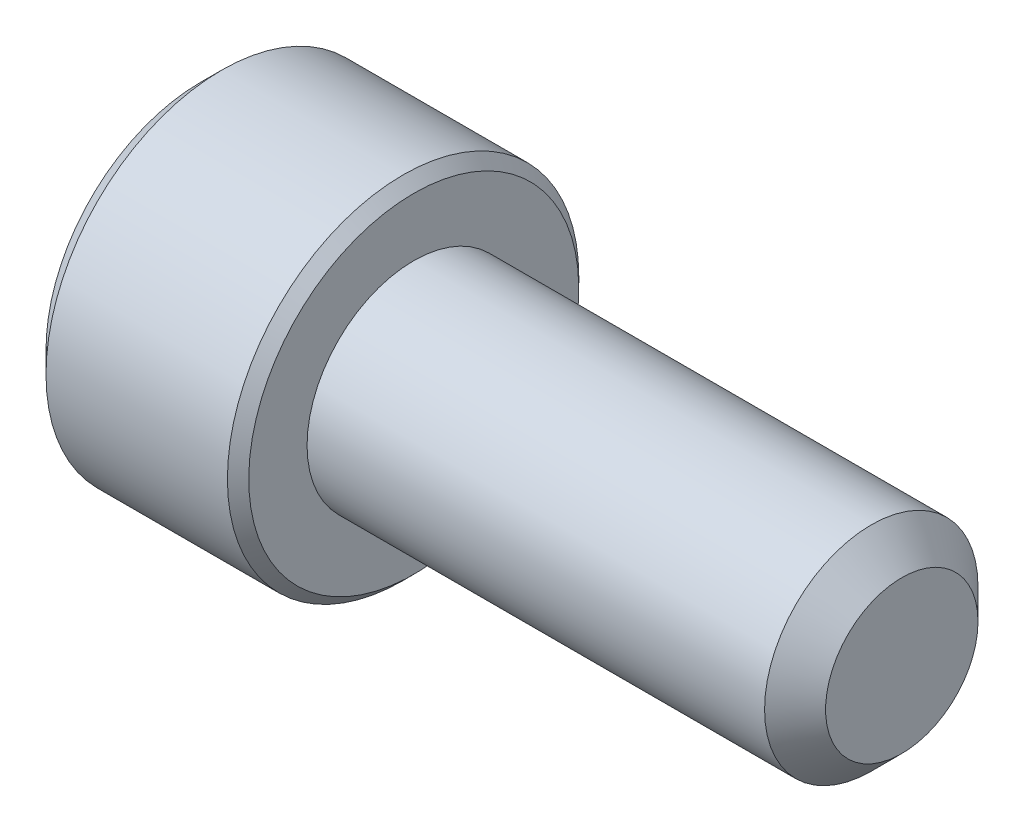
SolidWorks part; units mm, degrees
material "Alloy Steel"
ref_plane "Front Plane" through (0, 0, 0) normal (0, 0, 1) x (1, 0, 0)
ref_plane "Top Plane" through (0, 0, 0) normal (0, 1, 0) x (1, 0, 0)
ref_plane "Right Plane" through (0, 0, 0) normal (1, 0, 0) x (0, 0, -1)
sketch "Sketch1" plane through (0, 0, 0) normal (0, 0, 1) x (1, 0, 0)
  line L0 (4.7625, 0) -> (-4.7625, 0) construction
  line L1 (4.7625, 2.0828) -> (4.7625, -2.0828) construction
  line L2 (-4.7625, 3.2207) -> (-4.7625, -3.2207) construction
  line L3 (-4.9708, 3.429) -> (-8.5115, 3.429) construction
  line L4 (-8.5115, 3.429) -> (-8.9281, 3.0124) construction
  line L5 (-8.9281, 3.0124) -> (-8.9281, -3.0124) construction
  line L6 (-8.9281, -3.0124) -> (-8.5115, -3.429) construction
  line L7 (-8.5115, -3.429) -> (-4.9708, -3.429) construction
  line L8 (-4.9708, 3.429) -> (-4.7625, 3.2207) construction
  line L9 (-4.7625, -3.2207) -> (-4.9708, -3.429) construction
  point P5 (-4.7625, 3.429)
  point P6 (-4.7625, -3.429)
  point P7 (-6.2492, 0)
  point P12 (1.5875, -2.0828)
  dimension "D1" = 45
  dimension "D2" = 3.175
  dimension "D3" = 0.2083
ref_plane "Plane1" through (4.7625, 0, 0) normal (1, 0, 0) x (0, 0, -1)
ref_plane "Plane2" through (-8.9281, 0, 0) normal (1, 0, 0) x (0, 0, -1)
sketch "Sketch2" plane through (4.7625, 0, 0) normal (1, 0, 0) x (0, 0, -1)
  circle A0 centre (0, 0) radius 2.0828
extrude "Boss-Extrude1" add sketch "Sketch2" against normal up to vertex (9.525 mm away) up to point (-4.7625, 0, 0)
sketch "Sketch3" plane through (4.7625, 0, 0) normal (1, 0, 0) x (0, 0, -1)
  circle A0 centre (0, 0) radius 2.0828 construction
  circle A1 centre (0, 0) radius 2.0828
curve "Helix/Spiral1" pitch 0.7937 height 10.3187 turns 13 parameters "Pitch"=0.7937
chamfer "Chamfer1" distance 0.5953 angle 45 1 edges at (4.7625, 0, -2.0828)
sketch "Sketch5" plane through (0, 0, 0) normal (0, 0, 1) x (1, 0, 0)
  line L0 (4.4152, 2.0828) -> (5.1098, 2.0828)
  line L1 (5.1098, 2.0828) -> (4.8121, 1.5672)
  line L2 (4.8121, 1.5672) -> (4.7129, 1.5672)
  line L3 (4.7129, 1.5672) -> (4.4152, 2.0828)
  line L4 (4.7625, 1.5672) -> (4.7625, 2.0828) construction
  line L5 (4.5641, 1.825) -> (4.9609, 1.825) construction
  dimension "D1" = 60
  dimension "D2" = 0.3969
  dimension "D3" = 0.0992
sweep "Cut-Sweep1" [suppressed] cut profiles "Sketch5" path "Helix/Spiral1"
sketch "Sketch4" plane through (-8.9281, 0, 0) normal (1, 0, 0) x (0, 0, -1)
  line L0 (-3.429, 0.7937) -> (3.429, 0.7937) construction
  line L1 (0, 2.0622) -> (-1.7859, 1.0311)
  line L2 (-1.7859, 1.0311) -> (-1.7859, -1.0311)
  line L3 (-1.7859, -1.0311) -> (0, -2.0622)
  line L4 (0, -2.0622) -> (1.7859, -1.0311)
  line L5 (1.7859, -1.0311) -> (1.7859, 1.0311)
  line L6 (1.7859, 1.0311) -> (0, 2.0622)
  line L7 (0, 0) -> (0, 0.7937) construction
  circle A0 centre (0, 0) radius 1.7859 construction
  dimension "D1" = 6.858
  dimension "D2" = 0.7937
sketch "Sketch6" plane through (0, 0, 0) normal (0, 0, 1) x (1, 0, 0)
  line L0 (-8.5115, 3.429) -> (-8.9281, 3.0124) construction
  line L2 (-4.7625, 3.2207) -> (-4.7625, -3.2207) construction
  line L3 (-8.9281, 3.0124) -> (-8.9281, -3.0124) construction
  line L4 (-8.5115, 3.429) -> (-8.9281, 3.0124)
  line L5 (-4.9708, 3.429) -> (-8.5115, 3.429) construction
  line L6 (-4.7625, 3.2207) -> (-4.7625, 0)
  line L7 (-8.9281, 3.0124) -> (-8.9281, 0)
  line L8 (-4.7625, 0) -> (-8.9281, 0) construction
  line L9 (-4.7625, 0) -> (-8.9281, 0)
  line L10 (-4.9708, 3.429) -> (-4.7625, 3.2207) construction
  line L11 (-4.9708, 3.429) -> (-8.5115, 3.429)
  line L12 (-4.9708, 3.429) -> (-4.7625, 3.2207)
revolve "Revolve1" add sketch "Sketch6" angle 360 about L8
extrude "Cut-Extrude1" cut sketch "Sketch4" along normal up to vertex (2.6789 mm away) up to point (-6.2492, 0, 0)
sketch "Sketch8" plane through (-8.9281, 0, 0) normal (-1, 0, 0) x (0, 0, 1)
  circle A1 centre (0, 0) radius 2.0622
extrude "Cut-Extrude2" cut sketch "Sketch8" against normal blind 0.8331 draft 45
equation "\"D3@Helix/Spiral1\" = \"Length@Sketch1\"+\"Pitch@Helix/Spiral1\""
equation "\"D3@Sketch5\" = \"Pitch@Helix/Spiral1\"*.125"
equation "\"D2@Sketch5\" = \"Pitch@Helix/Spiral1\"*.50"
equation "\"D1@Chamfer1\" = \"Pitch@Helix/Spiral1\"*.75"
equation "\"D2@Sketch1\" = \"Pitch@Helix/Spiral1\"*4"
equation "\"D1@Sketch4\" = \"Head Dia@Sketch1\""
equation "\"Chamfer@Sketch1\" = \"Head Height@Sketch1\"/10"
equation "\"D3@Sketch1\" = \"Chamfer@Sketch1\"/2"
equation "\"D1@Cut-Extrude2\" = \"Chamfer@Sketch1\"*2"
